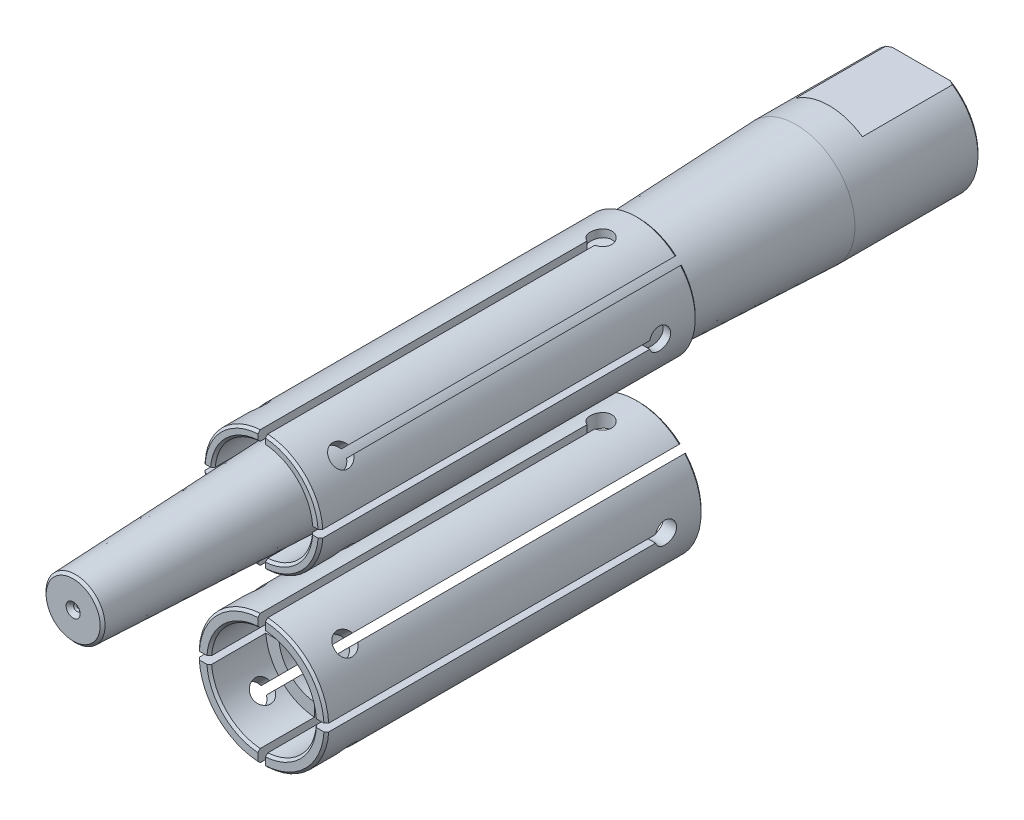
SolidWorks part; units mm, degrees
note: The reader was unsure of these and kept them because the rebuilt part matched: shared geometry of "Sketch2<3>".
ref_plane "Front Plane" through (0, 0, 0) normal (0, 0, 1) x (1, 0, 0)
ref_plane "Top Plane" through (0, 0, 0) normal (0, 1, 0) x (1, 0, 0)
ref_plane "Right Plane" through (0, 0, 0) normal (1, 0, 0) x (0, 0, -1)
sketch "Sketch1" plane through (0, 0, 0) normal (1, 0, 0) x (0, 0, -1)
  line L0 (-114.3, 0) -> (114.3, 0) construction
  line L1 (-63.5, 0) -> (38.1, 0) construction
  line L2 (-63.5, 15.875) -> (-63.5, -15.875) construction
  line L3 (-63.5, -19.05) -> (-63.5, 19.05) construction
  point P8 (-63.5, 0)
  dimension "Overall Length" = 228.6
  dimension "Sleeve Length" = 101.6
  dimension "D1" = 50.8
  dimension "OD Min" = 31.75
  dimension "OD Max" = 38.1
sketch "Sketch2" plane through (0, 0, 0) normal (1, 0, 0) x (0, 0, -1)
  line L0 (-114.3, 0) -> (114.3, 0) construction
  line L1 (-1114.3, 0) -> (-115.4901, 0) construction
  line L2 (109.22, 0) -> (-111.6012, 0)
  line L3 (-114.3, 1.905) -> (-114.3, 7.9375)
  line L4 (-114.3, 7.9375) -> (80.518, 15.875)
  line L5 (80.518, 15.875) -> (114.3, 15.875)
  line L6 (114.3, 15.875) -> (114.3, 2.54)
  line L7 (-63.5, 13.1682) -> (-63.5, 15.875)
  line L8 (-63.5, 15.875) -> (-63.5, -15.875) construction
  line L9 (-63.5, 10.0073) -> (38.1, 14.1468)
  line L10 (-63.5, 15.875) -> (38.1, 15.875)
  line L11 (38.1, 15.875) -> (38.1, 14.1468)
  line L12 (-114.3, 1.905) -> (-113.284, 0.889)
  line L13 (-113.284, 0.889) -> (-112.4902, 0.889)
  line L14 (-112.4902, 0.889) -> (-111.6012, 0)
  line L15 (114.3, 2.54) -> (111.76, 2.54)
  line L16 (111.76, 2.54) -> (109.22, 0)
  line L18 (-111.6012, 0) -> (109.22, 0) construction
  line L19 (-63.5, 13.1682) -> (-48.2592, 13.1682)
  line L20 (-48.2592, 13.1682) -> (-48.2592, 10.6282)
  dimension "D1" = 15.875
  dimension "D2" = 31.75
  dimension "D3" = 33.782
  dimension "D4" = 3.81
  dimension "D5" = 45
  dimension "D6" = 1.778
  dimension "D7" = 0.7937
  dimension "D8" = 45
  dimension "D9" = 2.54
  dimension "D10" = 15.2408
  dimension "D11" = 2.54
  dimension "D12" = 5.08
revolve "Revolve1" add sketch "Sketch2" angle 360 about L1
revolve "Revolve2" add sketch "Sketch2<3>" angle 360 about L1
sketch "Sketch2<3>" plane through (0, 0, 0) normal (1, 0, 0) x (0, 0, -1) same geometry as "Sketch2"
sketch "Sketch7" plane through (0, 0, 0) normal (1, 0, 0) x (0, 0, -1)
  line L0 (-114.3, 1.905) -> (-114.3, 7.9375) construction
  line L1 (-114.3, 1.905) -> (-113.284, 0.889) construction
  line L2 (-113.284, 0.889) -> (-112.4902, 0.889) construction
  line L3 (-112.4902, 0.889) -> (-111.6012, 0) construction
  line L4 (109.22, 0) -> (-111.6012, 0) construction
  line L5 (111.76, 2.54) -> (109.22, 0) construction
  line L6 (114.3, 2.54) -> (111.76, 2.54) construction
  line L7 (114.3, 15.875) -> (114.3, 2.54) construction
  line L8 (80.518, 15.875) -> (114.3, 15.875) construction
  line L9 (-114.3, 7.9375) -> (80.518, 15.875) construction
  line L10 (-114.3, 1.905) -> (-114.3, 7.9375) construction
  line L11 (-114.3, 1.905) -> (-113.284, 0.889) construction
  line L12 (-113.284, 0.889) -> (-112.4902, 0.889) construction
  line L13 (-112.4902, 0.889) -> (-111.6012, 0) construction
  line L14 (109.22, 0) -> (-111.6012, 0) construction
  line L15 (111.76, 2.54) -> (109.22, 0) construction
  line L16 (114.3, 2.54) -> (111.76, 2.54) construction
  line L17 (114.3, 15.875) -> (114.3, 2.54) construction
  line L18 (80.518, 15.875) -> (114.3, 15.875) construction
  line L19 (-114.3, 7.9375) -> (80.518, 15.875) construction
  line L20 (-114.3, -36.5125) -> (80.518, -28.575) construction
  line L21 (80.518, -28.575) -> (114.3, -28.575) construction
  line L22 (114.3, -28.575) -> (114.3, -41.91) construction
  line L23 (114.3, -41.91) -> (111.76, -41.91) construction
  line L24 (111.76, -41.91) -> (109.22, -44.45) construction
  line L25 (109.22, -44.45) -> (-111.6012, -44.45) construction
  line L26 (-112.4902, -43.561) -> (-111.6012, -44.45) construction
  line L27 (-113.284, -43.561) -> (-112.4902, -43.561) construction
  line L28 (-114.3, -42.545) -> (-113.284, -43.561) construction
  line L29 (-114.3, -42.545) -> (-114.3, -36.5125) construction
  line L30 (-63.5, -30.3032) -> (-63.5, -26.9875)
  line L31 (-63.5, -26.9875) -> (38.1, -26.9875)
  line L32 (38.1, -26.9875) -> (38.1, -30.3032)
  line L33 (38.1, -30.3032) -> (-48.2592, -33.8218)
  line L34 (-63.5, -30.3032) -> (-48.2592, -30.3032)
  line L35 (-48.2592, -30.3032) -> (-48.2592, -33.8218)
  line L36 (-63.5, 13.1682) -> (-48.2592, 13.1682) construction
  line L37 (-63.5, -61.9125) -> (38.1, -61.9125) construction
  dimension "D2" = 44.45
  dimension "D3" = 34.925
revolve "Revolve3" add sketch "Sketch7" angle 360 about L25
sketch "Sketch3" plane through (0, 0, 0) normal (1, 0, 0) x (0, 0, -1)
  line L0 (-114.3, 0) -> (114.3, 0) construction
  line L1 (114.3, 15.875) -> (89.408, 15.875)
  line L2 (114.3, 15.875) -> (114.3, 13.081)
  line L3 (114.3, 13.081) -> (89.408, 13.081)
  line L4 (89.408, 15.875) -> (89.408, 13.081)
  line L5 (-114.3, 0) -> (114.3, 0) construction
  dimension "D1" = 2.794
  dimension "D2" = 24.892
extrude "Cut-Extrude1" cut sketch "Sketch3" against normal through all both and the other way through all
chamfer "Chamfer2" distance 0.635 angle 45 3 edges at (15.875, 0, 63.5) (15.875, 0, -38.1) (13.1682, 0, 63.5)
chamfer "Chamfer3" distance 0.635 angle 45 3 edges at (0, -26.9875, -38.1) (0, -26.9875, 63.5) (0, -30.3032, 63.5)
sketch "Sketch4" plane through (0, 0, 0) normal (1, 0, 0) x (0, 0, -1)
  line L0 (-114.3, 0) -> (114.3, 0) construction
  line L1 (-114.3, 0) -> (114.3, 0) construction
  line L2 (-63.5, -1.016) -> (-63.5, 1.016)
  line L3 (-63.5, 15.875) -> (-63.5, -15.875) construction
  line L4 (-63.5, 1.016) -> (25.2285, 1.016)
  line L5 (-63.5, -1.016) -> (25.2285, -1.016)
  arc A0 (25.2285, 1.016) -> (25.2285, -1.016) centre (27.94, 0) cw
  point P10 (-63.5, 0)
  dimension "D3" = 2.8956
  dimension "D1" = 2.032
  dimension "D2" = 91.44
extrude "Cut-Extrude2" cut sketch "Sketch4" along normal through all both and the other way through all
ref_plane "Plane1" through (0, 0, 0) normal (0.7071, 0.7071, 0) x (0, 0, -1)
sketch "Sketch5" plane through (0, 0, 0) normal (0.7071, 0.7071, 0) x (0, 0, -1)
  line L0 (-201114.3, 0) -> (199884.5099, 0) construction
  line L1 (-201114.3, 0) -> (199884.5099, 0) construction
  line L2 (38.1, -1.016) -> (38.1, 1.016)
  line L3 (38.1, 1.016) -> (-50.6285, 1.016)
  line L4 (38.1, -1.016) -> (-50.6285, -1.016)
  arc A0 (-50.6285, 1.016) -> (-50.6285, -1.016) centre (-53.34, 0) ccw
  point P8 (38.1, 0)
  dimension "D3" = 2.8956
  dimension "D1" = 2.032
  dimension "D2" = 91.44
extrude "Cut-Extrude3" cut sketch "Sketch5" against normal through all both and the other way through all
pattern_circular "CirPattern1" count 2 every 90 about axis through (0, 0, 0) along (0, 0, 1) of "Cut-Extrude2", "Cut-Extrude3"
pattern_linear "LPattern2" count 2 spacing 44.45 along (0, -1, 0) of "Cut-Extrude3", "Cut-Extrude2"
pattern_circular "CirPattern2" count 2 every 90 about axis through (0, -44.45, 0) along (0, 0, 1) of "LPattern2"
chamfer "Chamfer1" distance 0.635 angle 45 3 edges at (7.9375, 0, 114.3) (2.54, 0, -114.3) (0, -15.875, -114.3)
sketch "Sketch6" plane through (0, 0, 0) normal (0, 0, 1) x (1, 0, 0)
  circle A0 centre (0, 0) radius 15.875
  circle A1 centre (0, -44.45) radius 17.4625
  dimension "D1" = 31.75
  dimension "D2" = 34.925
equation "\"D1@Sketch1\"=\"Overall Length@Sketch1\"*2/9"
equation "\"D1@Sketch5\"=\"D1@Sketch4\""
equation "\"D2@Sketch5\"=\"D2@Sketch4\""
equation "\"D3@Sketch5\"=\"D3@Sketch4\""
equation "\"D2@Sketch2\"=\"OD Min@Sketch1\""
equation "\"D1@Sketch2\"=\"D2@Sketch2\"*.5"
equation "\"D1@Chamfer2\"=\"OD Min@Sketch1\"*.02"
equation "\"D2@Sketch4\"=\"Sleeve Length@Sketch1\"*.9"
equation "\"D3@Sketch4\"=\"D1@Sketch4\"*2.85*.5"
equation "\"D1@Chamfer1\"=\"OD Min@Sketch1\"*.02"
equation "\"D3@Sketch7\"=\"OD Min@Sketch1\"+(\"OD Max@Sketch1\"-\"OD Min@Sketch1\")/2"
equation "\"D1@Chamfer3\"=\"D1@Chamfer2\""
equation "\"D3@LPattern1\"=\"D2@Sketch7\""
equation "\"D2@Sketch7\"=\"OD Min@Sketch1\"*1.4"
equation "\"D3@LPattern2\"=\"D2@Sketch7\""
equation "\"D10@Sketch2\"=\"Overall Length@Sketch1\"*.06667"
